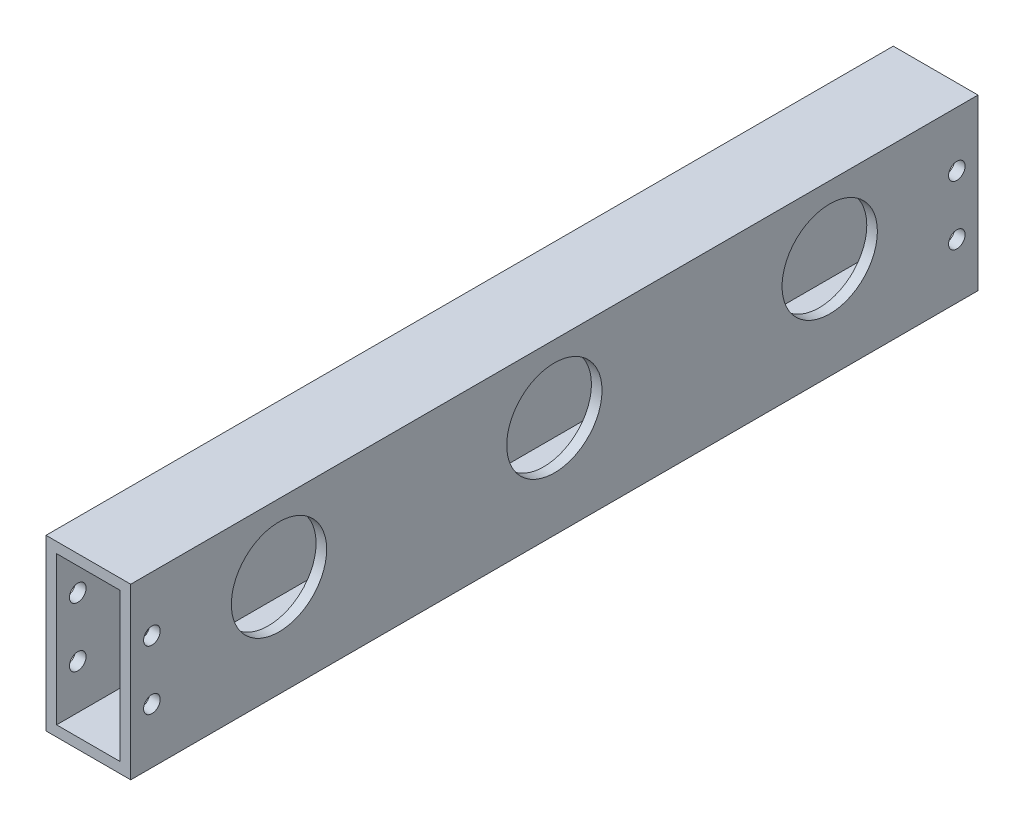
SolidWorks part; units mm, degrees
material "6061-T6 (SS)"
ref_plane "Front Plane" through (0, 0, 0) normal (0, 0, 1) x (1, 0, 0)
ref_plane "Top Plane" through (0, 0, 0) normal (0, 1, 0) x (1, 0, 0)
ref_plane "Right Plane" through (0, 0, 0) normal (1, 0, 0) x (0, 0, -1)
sketch "Sketch1" plane through (0, 0, 0) normal (1, 0, 0) x (0, 0, -1)
  line L1 (-127, 25.4) -> (127, 25.4)
  line L2 (-127, 25.4) -> (-127, -25.4)
  line L3 (-127, -25.4) -> (127, -25.4)
  line L4 (127, 25.4) -> (127, -25.4)
  line L5 (-127, 25.4) -> (127, -25.4) construction
  line L6 (-127, -25.4) -> (127, 25.4) construction
  point P0 (0, 0)
  dimension "D1" = 50.8
  dimension "D2" = 254
extrude "Boss-Extrude1" add sketch "Sketch1" along normal blind 25.4
shell "Shell1" thickness 3.175 removed face at (12.7, 0, -127) removed face at (12.7, 0, 127)
sketch "Sketch2" plane through (25.4, 0, 0) normal (1, 0, 0) x (0, 0, -1)
  line L0 (-127, -25.4) -> (127, -25.4) construction
  circle A0 centre (0, 5.08) radius 14.2875
  circle A1 centre (-82.55, 5.08) radius 14.2875
  circle A2 centre (82.55, 5.08) radius 14.2875
  circle A3 centre (-82.55, 5.08) radius 38.1 construction
  circle A4 centre (0, 5.08) radius 38.1 construction
  circle A5 centre (82.55, 5.08) radius 38.1 construction
  point P11 (0, 0)
  dimension "D1" = 28.575
  dimension "D5" = 76.2
  dimension "D2" = 30.48
  dimension "D3" = 82.55
  dimension "D4" = 82.55
  dimension "D6" = 0
extrude "Cut-Extrude1" cut sketch "Sketch2" against normal through all
sketch "Sketch3" plane through (25.4, 0, 0) normal (1, 0, 0) x (0, 0, -1)
  line L0 (-120.65, 8.89) -> (-120.65, -8.89) construction
  line L1 (-127, 25.4) -> (-127, -25.4) construction
  point P2 (-120.65, 0)
  point P3 (-127, 0)
  dimension "D1" = 17.78
  dimension "D2" = 6.35
hole_wizard "#10 Clearance Hole1" positions "Sketch4" profile "Sketch6" hole size "#10" standard "ANSI Inch" end condition through all
sketch "Sketch4" plane through (25.4, 0, 0) normal (1, 0, 0) x (0, 0, -1)
  point P0 (-120.65, 8.89)
  point P3 (-120.65, -8.89)
sketch "Sketch6" plane through (25.4, 8.89, 120.65) normal (0, 1, 0) x (0, 0, -1)
  line L0 (0, 0) -> (0, 25.4)
  line L1 (0, 25.4) -> (2.4892, 25.4)
  line L2 (2.4892, 25.4) -> (2.4892, 0)
  line L5 (2.4892, 0) -> (0, 0)
  line L11 (0, -6.35) -> (0, 107.95) construction
  dimension "Thru Hole Dia." = 4.9784
  dimension "Thru Hole Depth" = 25.4
mirror "Mirror1" about plane through (0, 0, 0) normal (0, 0, 1) of "#10 Clearance Hole1"
